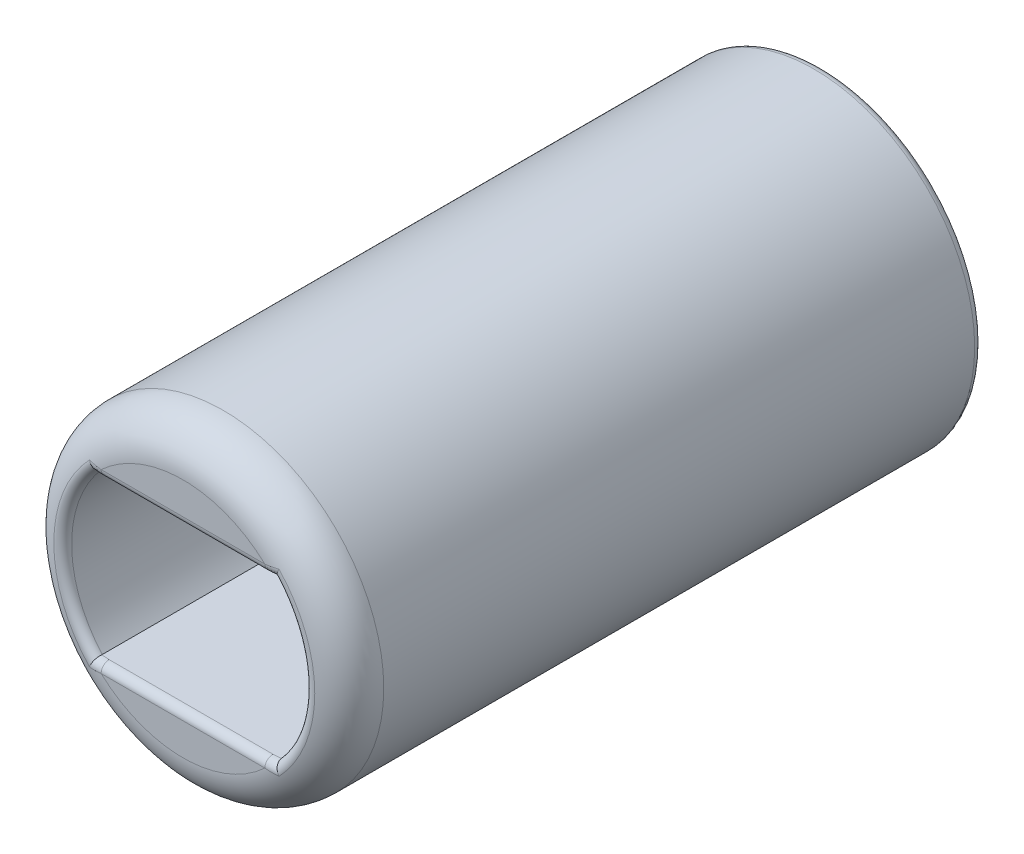
SolidWorks part; units mm, degrees
ref_plane "Front Plane" through (0, 0, 0) normal (0, 0, 1) x (1, 0, 0)
ref_plane "Top Plane" through (0, 0, 0) normal (0, 1, 0) x (1, 0, 0)
ref_plane "Right Plane" through (0, 0, 0) normal (1, 0, 0) x (0, 0, -1)
sketch "Sketch1" plane through (0, 0, 0) normal (0, 0, 1) x (1, 0, 0)
  line L1 (-8.6603, 5) -> (8.6603, 5)
  line L2 (-8.6603, 5) -> (-8.6603, -5)
  line L3 (-8.6603, -5) -> (8.6603, -5)
  line L4 (8.6603, 5) -> (8.6603, -5)
  line L5 (-8.6603, 5) -> (8.6603, -5) construction
  line L6 (-8.6603, -5) -> (8.6603, 5) construction
  circle A0 centre (0, 0) radius 7.5
  circle A1 centre (0, 0) radius 10
  dimension "D1" = 15
  dimension "D3" = 20
  dimension "D2" = 10
extrude "Boss-Extrude1" add sketch "Sketch1" against normal blind 39.8 contours L1 A0 | L1 A1 A0 | A0 L3 L4 L1 | L4 A1 | A0 L1 L2 L3 | L2 A1 | L3 A1 A0 | L3 A0
fillet "Fillet1" radius 2.5 1 edges at (10, 0, 0)
fillet "Fillet2" radius 0.5 1 edges at (10, 0, -39.8)
fillet "Fillet3" radius 0.5 6 edges at (0, 5, -39.8) (7.5, 0, -39.8) (0, -5, -39.8) (-7.5, 0, -39.8) (0, -5, 0) (0, 5, 0)
